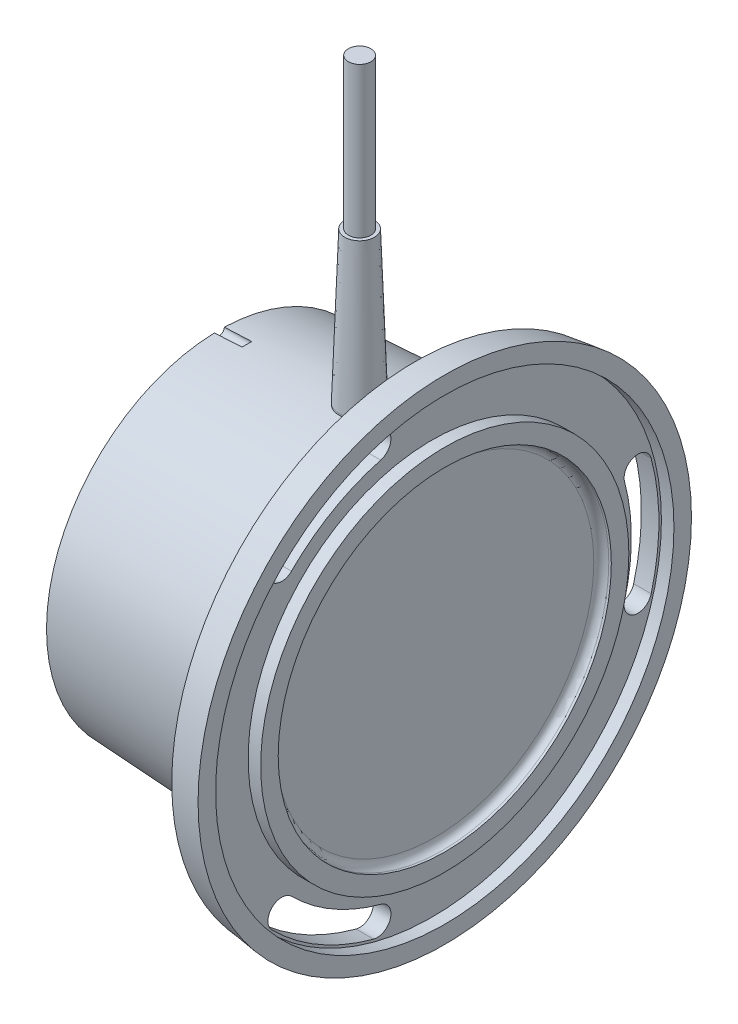
SolidWorks part; units mm, degrees
note: '?' marks a value the reader was unsure of.
ref_plane "Face" through (0, 0, 0) normal (0, 0, 1) x (1, 0, 0)
ref_plane "Dessus" through (0, 0, 0) normal (0, 1, 0) x (1, 0, 0)
ref_plane "Droite" through (0, 0, 0) normal (1, 0, 0) x (0, 0, -1)
sketch "Esquisse1" plane through (0, 0, 0) normal (0, 0, 1) x (1, 0, 0)
  line L0 (104.9224, 0) -> (-123.1954, 0) construction
  line L1 (0, 0) -> (0, 34.5)
  line L2 (0, 34.5) -> (39, 36.5)
  line L3 (39, 36.5) -> (39, 48.5)
  line L4 (39, 48.5) -> (45, 49.25)
  line L5 (45, 49.25) -> (45, 45.75)
  line L6 (43, 0) -> (0, 0)
  line L7 (45, 45.75) -> (42.5, 45.75)
  line L8 (42.5, 36.75) -> (45, 36.75)
  line L9 (42.5, 45.75) -> (42.5, 36.75)
  line L10 (45, 33.25) -> (44.5, 33.25)
  line L11 (43, 31.75) -> (43, 0)
  line L12 (45, 36.75) -> (45, 33.25)
  arc A0 (44.5, 33.25) -> (43, 31.75) centre (44.5, 31.75) ccw
  dimension "D12" = 1.5
  dimension "D1" = 45
  dimension "D2" = 6
  dimension "D3" = 49.25
  dimension "D4" = 48.5
  dimension "D5" = 36.5
  dimension "D6" = 34.5
  dimension "D7" = 3.5
  dimension "D8" = 3.5
  dimension "D9" = 12.5
  dimension "D10" = 3.5
  dimension "D11" = 2
revolve "Révolution1" add sketch "Esquisse1" angle 360 about L0
sketch "Esquisse2" plane through (0, 0, 0) normal (-1, 0, 0) x (0, 0, 1)
  circle A0 centre (0, 34.5) radius 1
  dimension "D2" = 2
  dimension "D1" = 34.5
extrude "Enlèv. mat.-Extru.1" cut sketch "Esquisse2" against normal blind 5.5
sketch "Esquisse3" plane through (0, 0, 0) normal (0, 1, 0) x (1, 0, 0)
  line L0 (45, -49.25) -> (45, 49.25) construction
  circle A0 centre (28, 0) radius 4
  dimension "D2" = 8
  dimension "D1" = 17
extrude "Extrusion1" add sketch "Esquisse3" along normal blind 36
sketch "Esquisse4" plane through (0, 36, 0) normal (0, 1, 0) x (-1, 0, 0)
  circle A0 centre (-28, 0) radius 4
extrude "Extrusion2" add sketch "Esquisse4" along normal blind 30 draft 2
sketch "Esquisse5" plane through (0, 66, 0) normal (0, 1, 0) x (-1, 0, 0)
  circle A0 centre (-28, 0) radius 2.25
  dimension "D1" = 4.5
extrude "Extrusion3" add sketch "Esquisse5" along normal blind 30
sketch "Esquisse6" plane through (39, 0, 0) normal (-1, 0, 0) x (0, 0, 1)
  line L0 (0, 0) -> (-77.3297, 0) construction
  arc A1 (-38.3955, 10.2882) -> (-43.7081, 11.7118) centre (-41.0518, 11) ccw
  arc A2 (-38.3955, -10.2882) -> (-43.7081, -11.7118) centre (-41.0518, -11) cw
  arc A3 (-43.7081, 11.7118) -> (-43.7081, -11.7118) centre (0, 0) ccw
  arc A4 (-38.3955, 10.2882) -> (-38.3955, -10.2882) centre (0, 0) ccw
  dimension "D1" = 42.5
  dimension "D2" = 5.5
  dimension "D3" = 11
extrude "Enlèv. mat.-Extru.2" cut sketch "Esquisse6" against normal through all
ref_axis "Axe1" through (39, 0, 0) along (-1, 0, 0)?
pattern_circular "Répétition circulaire1" count 3 every 120 about axis through (39, 0, 0) along (-1, 0, 0)
